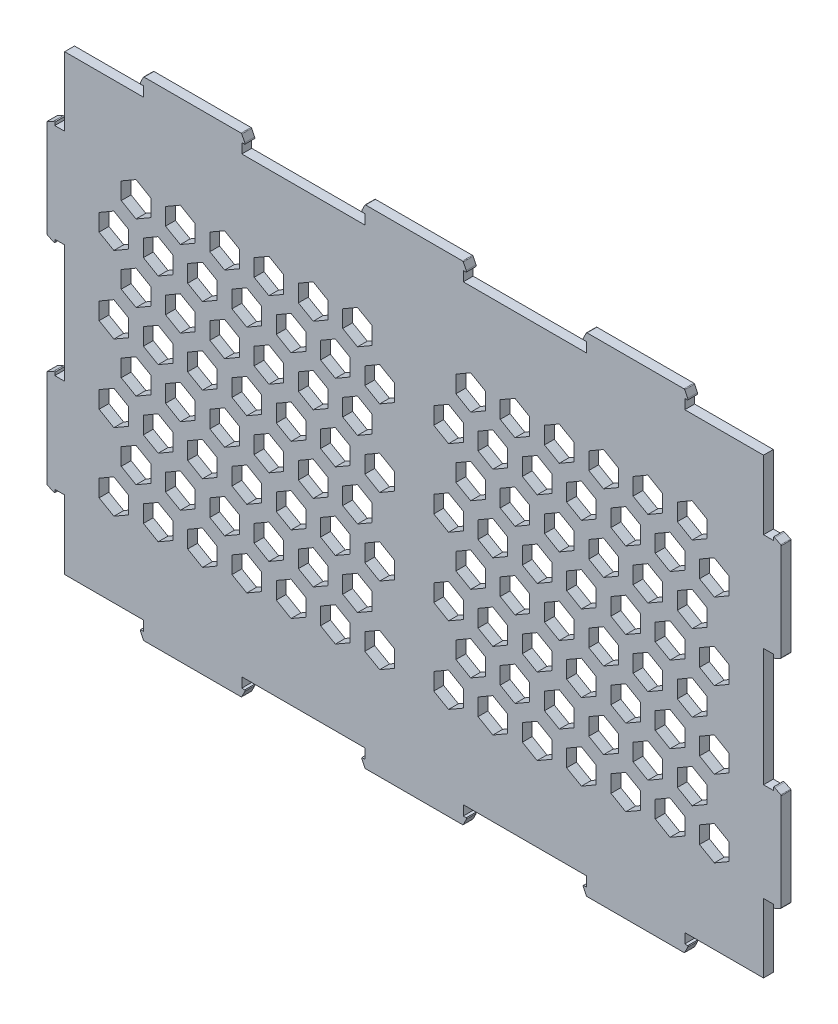
SolidWorks part; units mm, degrees
ref_plane "Front Plane" through (0, 0, 0) normal (0, 0, 1) x (1, 0, 0)
ref_plane "Top Plane" through (0, 0, 0) normal (0, 1, 0) x (1, 0, 0)
ref_plane "Right Plane" through (0, 0, 0) normal (1, 0, 0) x (0, 0, -1)
sketch "Sketch1" plane through (0, 0, 0) normal (0, 0, 1) x (1, 0, 0)
  line L0 (0, 0) -> (142, 0) construction
  line L1 (142, -46) -> (142, 46) construction
  line L2 (142, 46) -> (0, 46) construction
  line L3 (0, 46) -> (0, -46) construction
  line L8 (0, -46) -> (142, -46) construction
  line L30 (71, 46) -> (71, -46) construction
  line L31 (0, 32) -> (0, 46)
  line L32 (0, 46) -> (16, 46)
  line L35 (36, 46) -> (61, 46)
  line L37 (81, 46) -> (106, 46)
  line L39 (126, 46) -> (142, 46)
  line L40 (142, 46) -> (142, 32)
  line L42 (142, -32) -> (142, -46)
  line L43 (142, -46) -> (126, -46)
  line L46 (106, -46) -> (81, -46)
  line L48 (61, -46) -> (36, -46)
  line L50 (16, -46) -> (0, -46)
  line L51 (0, -46) -> (0, -32)
  line L52 (142, 46) -> (142, 32)
  line L54 (142, 12) -> (142, -12)
  line L56 (0, -12) -> (0, 12)
  line B0 (16, -46) -> (36, -46) construction
  line B1 (16.1618, -49.6) -> (35.8382, -49.6)
  line B2 (16, -46) -> (16, -48)
  line B3 (16, -49.5) -> (36, -49.5) construction
  line B4 (26, -49.5) -> (26, -46) construction
  line B5 (36, -46) -> (36, -48)
  line B6 (36.6, -48.3) -> (36, -49.5)
  line B7 (15.4, -48.3) -> (16, -49.5)
  line B8 (16, -48) -> (15.4, -48)
  line B9 (36, -48) -> (36.6, -48)
  arc B10 (16, -48) -> (15.4, -48.3) centre (15.7, -48.15) ccw construction
  arc B11 (16, -49.5) -> (16.1618, -49.6) centre (16.1618, -49.4191) ccw
  arc B12 (36, -49.5) -> (35.8382, -49.6) centre (35.8382, -49.4191) cw
  arc B13 (15.4, -48) -> (15.4, -48.3) centre (15.7, -48.15) ccw
  arc B14 (36.6, -48) -> (36.6, -48.3) centre (36.3, -48.15) cw
  line B15 (61, -46) -> (81, -46) construction
  line B16 (61.1618, -49.6) -> (80.8382, -49.6)
  line B17 (61, -46) -> (61, -48)
  line B18 (61, -49.5) -> (81, -49.5) construction
  line B19 (71, -49.5) -> (71, -46) construction
  line B20 (81, -46) -> (81, -48)
  line B21 (81.6, -48.3) -> (81, -49.5)
  line B22 (60.4, -48.3) -> (61, -49.5)
  line B23 (61, -48) -> (60.4, -48)
  line B24 (81, -48) -> (81.6, -48)
  arc B25 (61, -48) -> (60.4, -48.3) centre (60.7, -48.15) ccw construction
  arc B26 (61, -49.5) -> (61.1618, -49.6) centre (61.1618, -49.4191) ccw
  arc B27 (81, -49.5) -> (80.8382, -49.6) centre (80.8382, -49.4191) cw
  arc B28 (60.4, -48) -> (60.4, -48.3) centre (60.7, -48.15) ccw
  arc B29 (81.6, -48) -> (81.6, -48.3) centre (81.3, -48.15) cw
  line B30 (142, 12) -> (142, 32) construction
  line B31 (145.6, 12.1618) -> (145.6, 31.8382)
  line B32 (142, 12) -> (144, 12)
  line B33 (145.5, 12) -> (145.5, 32) construction
  line B34 (145.5, 22) -> (142, 22) construction
  line B35 (142, 32) -> (144, 32)
  line B36 (144.3, 32.6) -> (145.5, 32)
  line B37 (144.3, 11.4) -> (145.5, 12)
  line B38 (144, 12) -> (144, 11.4)
  line B39 (144, 32) -> (144, 32.6)
  arc B40 (144, 12) -> (144.3, 11.4) centre (144.15, 11.7) ccw construction
  arc B41 (145.5, 12) -> (145.6, 12.1618) centre (145.4191, 12.1618) ccw
  arc B42 (145.5, 32) -> (145.6, 31.8382) centre (145.4191, 31.8382) cw
  arc B43 (144, 11.4) -> (144.3, 11.4) centre (144.15, 11.7) ccw
  arc B44 (144, 32.6) -> (144.3, 32.6) centre (144.15, 32.3) cw
  line B45 (126, -46) -> (106, -46) construction
  line B46 (125.8382, -49.6) -> (106.1618, -49.6)
  line B47 (126, -46) -> (126, -48)
  line B48 (126, -49.5) -> (106, -49.5) construction
  line B49 (116, -49.5) -> (116, -46) construction
  line B50 (106, -46) -> (106, -48)
  line B51 (105.4, -48.3) -> (106, -49.5)
  line B52 (126.6, -48.3) -> (126, -49.5)
  line B53 (126, -48) -> (126.6, -48)
  line B54 (106, -48) -> (105.4, -48)
  arc B55 (126, -48) -> (126.6, -48.3) centre (126.3, -48.15) cw construction
  arc B56 (126, -49.5) -> (125.8382, -49.6) centre (125.8382, -49.4191) cw
  arc B57 (106, -49.5) -> (106.1618, -49.6) centre (106.1618, -49.4191) ccw
  arc B58 (126.6, -48) -> (126.6, -48.3) centre (126.3, -48.15) cw
  arc B59 (105.4, -48) -> (105.4, -48.3) centre (105.7, -48.15) ccw
  line B60 (16, 46) -> (36, 46) construction
  line B61 (16.1618, 49.6) -> (35.8382, 49.6)
  line B62 (16, 46) -> (16, 48)
  line B63 (16, 49.5) -> (36, 49.5) construction
  line B64 (26, 49.5) -> (26, 46) construction
  line B65 (36, 46) -> (36, 48)
  line B66 (36.6, 48.3) -> (36, 49.5)
  line B67 (15.4, 48.3) -> (16, 49.5)
  line B68 (16, 48) -> (15.4, 48)
  line B69 (36, 48) -> (36.6, 48)
  arc B70 (16, 48) -> (15.4, 48.3) centre (15.7, 48.15) cw construction
  arc B71 (16, 49.5) -> (16.1618, 49.6) centre (16.1618, 49.4191) cw
  arc B72 (36, 49.5) -> (35.8382, 49.6) centre (35.8382, 49.4191) ccw
  arc B73 (15.4, 48) -> (15.4, 48.3) centre (15.7, 48.15) cw
  arc B74 (36.6, 48) -> (36.6, 48.3) centre (36.3, 48.15) ccw
  line B75 (61, 46) -> (81, 46) construction
  line B76 (61.1618, 49.6) -> (80.8382, 49.6)
  line B77 (61, 46) -> (61, 48)
  line B78 (61, 49.5) -> (81, 49.5) construction
  line B79 (71, 49.5) -> (71, 46) construction
  line B80 (81, 46) -> (81, 48)
  line B81 (81.6, 48.3) -> (81, 49.5)
  line B82 (60.4, 48.3) -> (61, 49.5)
  line B83 (61, 48) -> (60.4, 48)
  line B84 (81, 48) -> (81.6, 48)
  arc B85 (61, 48) -> (60.4, 48.3) centre (60.7, 48.15) cw construction
  arc B86 (61, 49.5) -> (61.1618, 49.6) centre (61.1618, 49.4191) cw
  arc B87 (81, 49.5) -> (80.8382, 49.6) centre (80.8382, 49.4191) ccw
  arc B88 (60.4, 48) -> (60.4, 48.3) centre (60.7, 48.15) cw
  arc B89 (81.6, 48) -> (81.6, 48.3) centre (81.3, 48.15) ccw
  line B90 (126, 46) -> (106, 46) construction
  line B91 (125.8382, 49.6) -> (106.1618, 49.6)
  line B92 (126, 46) -> (126, 48)
  line B93 (126, 49.5) -> (106, 49.5) construction
  line B94 (116, 49.5) -> (116, 46) construction
  line B95 (106, 46) -> (106, 48)
  line B96 (105.4, 48.3) -> (106, 49.5)
  line B97 (126.6, 48.3) -> (126, 49.5)
  line B98 (126, 48) -> (126.6, 48)
  line B99 (106, 48) -> (105.4, 48)
  arc B100 (126, 48) -> (126.6, 48.3) centre (126.3, 48.15) ccw construction
  arc B101 (126, 49.5) -> (125.8382, 49.6) centre (125.8382, 49.4191) ccw
  arc B102 (106, 49.5) -> (106.1618, 49.6) centre (106.1618, 49.4191) cw
  arc B103 (126.6, 48) -> (126.6, 48.3) centre (126.3, 48.15) ccw
  arc B104 (105.4, 48) -> (105.4, 48.3) centre (105.7, 48.15) cw
  line B105 (0, 12) -> (0, 32) construction
  line B106 (-3.6, 12.1618) -> (-3.6, 31.8382)
  line B107 (0, 12) -> (-2, 12)
  line B108 (-3.5, 12) -> (-3.5, 32) construction
  line B109 (-3.5, 22) -> (0, 22) construction
  line B110 (0, 32) -> (-2, 32)
  line B111 (-2.3, 32.6) -> (-3.5, 32)
  line B112 (-2.3, 11.4) -> (-3.5, 12)
  line B113 (-2, 12) -> (-2, 11.4)
  line B114 (-2, 32) -> (-2, 32.6)
  arc B115 (-2, 12) -> (-2.3, 11.4) centre (-2.15, 11.7) cw construction
  arc B116 (-3.5, 12) -> (-3.6, 12.1618) centre (-3.4191, 12.1618) cw
  arc B117 (-3.5, 32) -> (-3.6, 31.8382) centre (-3.4191, 31.8382) ccw
  arc B118 (-2, 11.4) -> (-2.3, 11.4) centre (-2.15, 11.7) cw
  arc B119 (-2, 32.6) -> (-2.3, 32.6) centre (-2.15, 32.3) ccw
  line B120 (0, -12) -> (0, -32) construction
  line B121 (-3.6, -12.1618) -> (-3.6, -31.8382)
  line B122 (0, -12) -> (-2, -12)
  line B123 (-3.5, -12) -> (-3.5, -32) construction
  line B124 (-3.5, -22) -> (0, -22) construction
  line B125 (0, -32) -> (-2, -32)
  line B126 (-2.3, -32.6) -> (-3.5, -32)
  line B127 (-2.3, -11.4) -> (-3.5, -12)
  line B128 (-2, -12) -> (-2, -11.4)
  line B129 (-2, -32) -> (-2, -32.6)
  arc B130 (-2, -12) -> (-2.3, -11.4) centre (-2.15, -11.7) ccw construction
  arc B131 (-3.5, -12) -> (-3.6, -12.1618) centre (-3.4191, -12.1618) ccw
  arc B132 (-3.5, -32) -> (-3.6, -31.8382) centre (-3.4191, -31.8382) cw
  arc B133 (-2, -11.4) -> (-2.3, -11.4) centre (-2.15, -11.7) ccw
  arc B134 (-2, -32.6) -> (-2.3, -32.6) centre (-2.15, -32.3) cw
  line B135 (142, -12) -> (142, -32) construction
  line B136 (145.6, -12.1618) -> (145.6, -31.8382)
  line B137 (142, -12) -> (144, -12)
  line B138 (145.5, -12) -> (145.5, -32) construction
  line B139 (145.5, -22) -> (142, -22) construction
  line B140 (142, -32) -> (144, -32)
  line B141 (144.3, -32.6) -> (145.5, -32)
  line B142 (144.3, -11.4) -> (145.5, -12)
  line B143 (144, -12) -> (144, -11.4)
  line B144 (144, -32) -> (144, -32.6)
  arc B145 (144, -12) -> (144.3, -11.4) centre (144.15, -11.7) cw construction
  arc B146 (145.5, -12) -> (145.6, -12.1618) centre (145.4191, -12.1618) cw
  arc B147 (145.5, -32) -> (145.6, -31.8382) centre (145.4191, -31.8382) ccw
  arc B148 (144, -11.4) -> (144.3, -11.4) centre (144.15, -11.7) cw
  arc B149 (144, -32.6) -> (144.3, -32.6) centre (144.15, -32.3) ccw
  dimension "D2" = 22
  dimension "D3" = 45
  dimension "D1" = 142
  dimension "D4" = 92
sketch_block_instance "insert_bloquant_20mm-2mm-1"
sketch_block "insert_bloquant_20mm-2mm" parameters "D1"=2, "D2"=1.5, "D3"=1.2, "D4"=20, "D5"=0.1, "D6"=0.6
sketch_block_instance "insert_bloquant_20mm-2mm-2"
sketch_block_instance "insert_bloquant_20mm-2mm-4"
sketch_block_instance "insert_bloquant_20mm-2mm-6"
sketch_block_instance "insert_bloquant_20mm-2mm-7"
sketch_block_instance "insert_bloquant_20mm-2mm-8"
sketch_block_instance "insert_bloquant_20mm-2mm-9"
sketch_block_instance "insert_bloquant_20mm-2mm-13"
sketch_block_instance "insert_bloquant_20mm-2mm-14"
sketch_block_instance "insert_bloquant_20mm-2mm-15"
extrude "Boss-Extrude1" add sketch "Sketch1" along normal blind 2 contours B114 B119 B111 B117 B106 B116 B112 B118 B113 B107 L51 L50 B2 B8 B13 B7 B11 B1 B12 B6 B14 B9 B5 L48 B17 B23 B28 B22 B26 B16 B27 B21 B29 B24 B20 L46 B50 B54 B59 B51 B57 B46 B56 B52 B58 B53 B47 L43 L42 B32 B38 region at (71, 0, 0)
sketch "Esquisse1" plane through (0, 0, 2) normal (0, 0, 1) x (1, 0, 0)
  line L0 (142, 0) -> (0, 0) construction
  line L3 (84, 2.1651) -> (85.5, -2.1651) construction
  line L4 (142, 12) -> (142, -12) construction
  line L5 (71, 49.6) -> (71, -49.6) construction
  line L6 (61.1618, 49.6) -> (80.8382, 49.6) construction
  line L7 (61.1618, -49.6) -> (80.8382, -49.6) construction
  point P8 (84.75, 0)
  line B0 (135, 5.6292) -> (132, 7.3612)
  line B1 (132, 7.3612) -> (129, 5.6292)
  line B2 (124.5, 9.9593) -> (127.5, 8.2272)
  line B3 (130.5, 9.9593) -> (130.5, 13.4234)
  line B4 (130.5, 13.4234) -> (127.5, 15.1554)
  line B5 (127.5, 15.1554) -> (124.5, 13.4234)
  line B6 (126, 2.1651) -> (126, 5.6292)
  line B7 (126, 5.6292) -> (123, 7.3612)
  line B8 (123, 7.3612) -> (120, 5.6292)
  line B9 (115.5, 9.9593) -> (118.5, 8.2272)
  line B10 (121.5, 9.9593) -> (121.5, 13.4234)
  line B11 (121.5, 13.4234) -> (118.5, 15.1554)
  line B12 (118.5, 15.1554) -> (115.5, 13.4234)
  line B13 (111, 2.1651) -> (114, 0.433)
  line B14 (117, 2.1651) -> (117, 5.6292)
  line B15 (117, 5.6292) -> (114, 7.3612)
  line B16 (114, 7.3612) -> (111, 5.6292)
  line B17 (106.5, 9.9593) -> (109.5, 8.2272)
  line B18 (112.5, 9.9593) -> (112.5, 13.4234)
  line B19 (112.5, 13.4234) -> (109.5, 15.1554)
  line B20 (109.5, 15.1554) -> (106.5, 13.4234)
  line B21 (102, 2.1651) -> (105, 0.433)
  line B22 (99, 2.1651) -> (99, 5.6292)
  line B23 (132, 0.433) -> (135, 2.1651)
  line B24 (108, 2.1651) -> (108, 5.6292)
  line B25 (108, 5.6292) -> (105, 7.3612)
  line B26 (105, 7.3612) -> (102, 5.6292)
  line B27 (99, 5.6292) -> (96, 7.3612)
  line B28 (96, 7.3612) -> (93, 5.6292)
  line B29 (88.5, 9.9593) -> (91.5, 8.2272)
  line B30 (94.5, 9.9593) -> (94.5, 13.4234)
  line B31 (94.5, 13.4234) -> (91.5, 15.1554)
  line B32 (91.5, 15.1554) -> (88.5, 13.4234)
  line B33 (84, 2.1651) -> (87, 0.433)
  line B34 (90, 2.1651) -> (90, 5.6292)
  line B35 (90, 5.6292) -> (87, 7.3612)
  line B36 (87, 7.3612) -> (84, 5.6292)
  line B37 (79.5, 9.9593) -> (82.5, 8.2272)
  line B38 (85.5, 9.9593) -> (85.5, 13.4234)
  line B39 (85.5, 13.4234) -> (82.5, 15.1554)
  line B40 (82.5, 15.1554) -> (79.5, 13.4234)
  line B41 (75, 2.1651) -> (78, 0.433)
  line B42 (81, 2.1651) -> (81, 5.6292)
  line B43 (81, 5.6292) -> (78, 7.3612)
  line B44 (78, 7.3612) -> (75, 5.6292)
  line B45 (103.5, 13.4234) -> (100.5, 15.1554)
  line B46 (100.5, 15.1554) -> (97.5, 13.4234)
  line B47 (129, 2.1651) -> (132, 0.433)
  line B48 (135, 2.1651) -> (135, 5.6292)
  line B49 (129, 5.6292) -> (129, 2.1651)
  line B50 (127.5, 8.2272) -> (130.5, 9.9593)
  line B51 (124.5, 13.4234) -> (124.5, 9.9593)
  line B52 (84, 5.6292) -> (84, 2.1651)
  line B53 (87, 0.433) -> (90, 2.1651)
  line B54 (102, 5.6292) -> (102, 2.1651)
  line B55 (105, 0.433) -> (108, 2.1651)
  line B56 (120, 5.6292) -> (120, 2.1651)
  line B57 (120, 2.1651) -> (123, 0.433)
  line B58 (123, 0.433) -> (126, 2.1651)
  line B59 (115.5, 13.4234) -> (115.5, 9.9593)
  line B60 (118.5, 8.2272) -> (121.5, 9.9593)
  line B61 (78, 0.433) -> (81, 2.1651)
  line B62 (75, 5.6292) -> (75, 2.1651)
  line B63 (82.5, 8.2272) -> (85.5, 9.9593)
  line B64 (79.5, 13.4234) -> (79.5, 9.9593)
  line B65 (96, 0.433) -> (99, 2.1651)
  line B66 (93, 2.1651) -> (96, 0.433)
  line B67 (93, 5.6292) -> (93, 2.1651)
  line B68 (91.5, 8.2272) -> (94.5, 9.9593)
  line B69 (88.5, 13.4234) -> (88.5, 9.9593)
  line B70 (100.5, 8.2272) -> (103.5, 9.9593)
  line B71 (97.5, 9.9593) -> (100.5, 8.2272)
  line B72 (97.5, 13.4234) -> (97.5, 9.9593)
  line B73 (103.5, 9.9593) -> (103.5, 13.4234)
  line B74 (114, 0.433) -> (117, 2.1651)
  line B75 (111, 5.6292) -> (111, 2.1651)
  line B76 (109.5, 8.2272) -> (112.5, 9.9593)
  line B77 (106.5, 13.4234) -> (106.5, 9.9593)
  line B78 (135, 21.2176) -> (132, 22.9497)
  line B79 (132, 22.9497) -> (129, 21.2176)
  line B80 (124.5, 25.5477) -> (127.5, 23.8157)
  line B81 (130.5, 25.5477) -> (130.5, 29.0119)
  line B82 (130.5, 29.0119) -> (127.5, 30.7439)
  line B83 (127.5, 30.7439) -> (124.5, 29.0119)
  line B84 (126, 17.7535) -> (126, 21.2176)
  line B85 (126, 21.2176) -> (123, 22.9497)
  line B86 (123, 22.9497) -> (120, 21.2176)
  line B87 (115.5, 25.5477) -> (118.5, 23.8157)
  line B88 (121.5, 25.5477) -> (121.5, 29.0119)
  line B89 (121.5, 29.0119) -> (118.5, 30.7439)
  line B90 (118.5, 30.7439) -> (115.5, 29.0119)
  line B91 (111, 17.7535) -> (114, 16.0215)
  line B92 (117, 17.7535) -> (117, 21.2176)
  line B93 (117, 21.2176) -> (114, 22.9497)
  line B94 (114, 22.9497) -> (111, 21.2176)
  line B95 (106.5, 25.5477) -> (109.5, 23.8157)
  line B96 (112.5, 25.5477) -> (112.5, 29.0119)
  line B97 (112.5, 29.0119) -> (109.5, 30.7439)
  line B98 (109.5, 30.7439) -> (106.5, 29.0119)
  line B99 (102, 17.7535) -> (105, 16.0215)
  line B100 (99, 17.7535) -> (99, 21.2176)
  line B101 (132, 16.0215) -> (135, 17.7535)
  line B102 (108, 17.7535) -> (108, 21.2176)
  line B103 (108, 21.2176) -> (105, 22.9497)
  line B104 (105, 22.9497) -> (102, 21.2176)
  line B105 (99, 21.2176) -> (96, 22.9497)
  line B106 (96, 22.9497) -> (93, 21.2176)
  line B107 (88.5, 25.5477) -> (91.5, 23.8157)
  line B108 (94.5, 25.5477) -> (94.5, 29.0119)
  line B109 (94.5, 29.0119) -> (91.5, 30.7439)
  line B110 (91.5, 30.7439) -> (88.5, 29.0119)
  line B111 (84, 17.7535) -> (87, 16.0215)
  line B112 (90, 17.7535) -> (90, 21.2176)
  line B113 (90, 21.2176) -> (87, 22.9497)
  line B114 (87, 22.9497) -> (84, 21.2176)
  line B115 (79.5, 25.5477) -> (82.5, 23.8157)
  line B116 (85.5, 25.5477) -> (85.5, 29.0119)
  line B117 (85.5, 29.0119) -> (82.5, 30.7439)
  line B118 (82.5, 30.7439) -> (79.5, 29.0119)
  line B119 (75, 17.7535) -> (78, 16.0215)
  line B120 (81, 17.7535) -> (81, 21.2176)
  line B121 (81, 21.2176) -> (78, 22.9497)
  line B122 (78, 22.9497) -> (75, 21.2176)
  line B123 (103.5, 29.0119) -> (100.5, 30.7439)
  line B124 (100.5, 30.7439) -> (97.5, 29.0119)
  line B125 (129, 17.7535) -> (132, 16.0215)
  line B126 (135, 17.7535) -> (135, 21.2176)
  line B127 (129, 21.2176) -> (129, 17.7535)
  line B128 (127.5, 23.8157) -> (130.5, 25.5477)
  line B129 (124.5, 29.0119) -> (124.5, 25.5477)
  line B130 (84, 21.2176) -> (84, 17.7535)
  line B131 (87, 16.0215) -> (90, 17.7535)
  line B132 (102, 21.2176) -> (102, 17.7535)
  line B133 (105, 16.0215) -> (108, 17.7535)
  line B134 (120, 21.2176) -> (120, 17.7535)
  line B135 (120, 17.7535) -> (123, 16.0215)
  line B136 (123, 16.0215) -> (126, 17.7535)
  line B137 (115.5, 29.0119) -> (115.5, 25.5477)
  line B138 (118.5, 23.8157) -> (121.5, 25.5477)
  line B139 (78, 16.0215) -> (81, 17.7535)
  line B140 (75, 21.2176) -> (75, 17.7535)
  line B141 (82.5, 23.8157) -> (85.5, 25.5477)
  line B142 (79.5, 29.0119) -> (79.5, 25.5477)
  line B143 (96, 16.0215) -> (99, 17.7535)
  line B144 (93, 17.7535) -> (96, 16.0215)
  line B145 (93, 21.2176) -> (93, 17.7535)
  line B146 (91.5, 23.8157) -> (94.5, 25.5477)
  line B147 (88.5, 29.0119) -> (88.5, 25.5477)
  line B148 (100.5, 23.8157) -> (103.5, 25.5477)
  line B149 (97.5, 25.5477) -> (100.5, 23.8157)
  line B150 (97.5, 29.0119) -> (97.5, 25.5477)
  line B151 (103.5, 25.5477) -> (103.5, 29.0119)
  line B152 (114, 16.0215) -> (117, 17.7535)
  line B153 (111, 21.2176) -> (111, 17.7535)
  line B154 (109.5, 23.8157) -> (112.5, 25.5477)
  line B155 (106.5, 29.0119) -> (106.5, 25.5477)
  line B156 (135, -25.5477) -> (132, -23.8157)
  line B157 (132, -23.8157) -> (129, -25.5477)
  line B158 (124.5, -21.2176) -> (127.5, -22.9497)
  line B159 (130.5, -21.2176) -> (130.5, -17.7535)
  line B160 (130.5, -17.7535) -> (127.5, -16.0215)
  line B161 (127.5, -16.0215) -> (124.5, -17.7535)
  line B162 (126, -29.0119) -> (126, -25.5477)
  line B163 (126, -25.5477) -> (123, -23.8157)
  line B164 (123, -23.8157) -> (120, -25.5477)
  line B165 (115.5, -21.2176) -> (118.5, -22.9497)
  line B166 (121.5, -21.2176) -> (121.5, -17.7535)
  line B167 (121.5, -17.7535) -> (118.5, -16.0215)
  line B168 (118.5, -16.0215) -> (115.5, -17.7535)
  line B169 (111, -29.0119) -> (114, -30.7439)
  line B170 (117, -29.0119) -> (117, -25.5477)
  line B171 (117, -25.5477) -> (114, -23.8157)
  line B172 (114, -23.8157) -> (111, -25.5477)
  line B173 (106.5, -21.2176) -> (109.5, -22.9497)
  line B174 (112.5, -21.2176) -> (112.5, -17.7535)
  line B175 (112.5, -17.7535) -> (109.5, -16.0215)
  line B176 (109.5, -16.0215) -> (106.5, -17.7535)
  line B177 (102, -29.0119) -> (105, -30.7439)
  line B178 (99, -29.0119) -> (99, -25.5477)
  line B179 (132, -30.7439) -> (135, -29.0119)
  line B180 (108, -29.0119) -> (108, -25.5477)
  line B181 (108, -25.5477) -> (105, -23.8157)
  line B182 (105, -23.8157) -> (102, -25.5477)
  line B183 (99, -25.5477) -> (96, -23.8157)
  line B184 (96, -23.8157) -> (93, -25.5477)
  line B185 (88.5, -21.2176) -> (91.5, -22.9497)
  line B186 (94.5, -21.2176) -> (94.5, -17.7535)
  line B187 (94.5, -17.7535) -> (91.5, -16.0215)
  line B188 (91.5, -16.0215) -> (88.5, -17.7535)
  line B189 (84, -29.0119) -> (87, -30.7439)
  line B190 (90, -29.0119) -> (90, -25.5477)
  line B191 (90, -25.5477) -> (87, -23.8157)
  line B192 (87, -23.8157) -> (84, -25.5477)
  line B193 (79.5, -21.2176) -> (82.5, -22.9497)
  line B194 (85.5, -21.2176) -> (85.5, -17.7535)
  line B195 (85.5, -17.7535) -> (82.5, -16.0215)
  line B196 (82.5, -16.0215) -> (79.5, -17.7535)
  line B197 (75, -29.0119) -> (78, -30.7439)
  line B198 (81, -29.0119) -> (81, -25.5477)
  line B199 (81, -25.5477) -> (78, -23.8157)
  line B200 (78, -23.8157) -> (75, -25.5477)
  line B201 (103.5, -17.7535) -> (100.5, -16.0215)
  line B202 (100.5, -16.0215) -> (97.5, -17.7535)
  line B203 (129, -29.0119) -> (132, -30.7439)
  line B204 (135, -29.0119) -> (135, -25.5477)
  line B205 (129, -25.5477) -> (129, -29.0119)
  line B206 (127.5, -22.9497) -> (130.5, -21.2176)
  line B207 (124.5, -17.7535) -> (124.5, -21.2176)
  line B208 (84, -25.5477) -> (84, -29.0119)
  line B209 (87, -30.7439) -> (90, -29.0119)
  line B210 (102, -25.5477) -> (102, -29.0119)
  line B211 (105, -30.7439) -> (108, -29.0119)
  line B212 (132, -27.2798) -> (75, -27.2798) construction
  line B213 (120, -25.5477) -> (120, -29.0119)
  line B214 (120, -29.0119) -> (123, -30.7439)
  line B215 (123, -30.7439) -> (126, -29.0119)
  line B216 (115.5, -17.7535) -> (115.5, -21.2176)
  line B217 (118.5, -22.9497) -> (121.5, -21.2176)
  line B218 (78, -30.7439) -> (81, -29.0119)
  line B219 (75, -25.5477) -> (75, -29.0119)
  line B220 (82.5, -22.9497) -> (85.5, -21.2176)
  line B221 (79.5, -17.7535) -> (79.5, -21.2176)
  line B222 (96, -30.7439) -> (99, -29.0119)
  line B223 (93, -29.0119) -> (96, -30.7439)
  line B224 (93, -25.5477) -> (93, -29.0119)
  line B225 (91.5, -22.9497) -> (94.5, -21.2176)
  line B226 (88.5, -17.7535) -> (88.5, -21.2176)
  line B227 (100.5, -22.9497) -> (103.5, -21.2176)
  line B228 (97.5, -21.2176) -> (100.5, -22.9497)
  line B229 (97.5, -17.7535) -> (97.5, -21.2176)
  line B230 (103.5, -21.2176) -> (103.5, -17.7535)
  line B231 (114, -30.7439) -> (117, -29.0119)
  line B232 (111, -25.5477) -> (111, -29.0119)
  line B233 (109.5, -22.9497) -> (112.5, -21.2176)
  line B234 (106.5, -17.7535) -> (106.5, -21.2176)
  line B235 (135, -9.9593) -> (132, -8.2272)
  line B236 (132, -8.2272) -> (129, -9.9593)
  line B237 (124.5, -5.6292) -> (127.5, -7.3612)
  line B238 (130.5, -5.6292) -> (130.5, -2.1651)
  line B239 (130.5, -2.1651) -> (127.5, -0.433)
  line B240 (127.5, -0.433) -> (124.5, -2.1651)
  line B241 (126, -13.4234) -> (126, -9.9593)
  line B242 (126, -9.9593) -> (123, -8.2272)
  line B243 (123, -8.2272) -> (120, -9.9593)
  line B244 (115.5, -5.6292) -> (118.5, -7.3612)
  line B245 (121.5, -5.6292) -> (121.5, -2.1651)
  line B246 (121.5, -2.1651) -> (118.5, -0.433)
  line B247 (118.5, -0.433) -> (115.5, -2.1651)
  line B248 (111, -13.4234) -> (114, -15.1554)
  line B249 (117, -13.4234) -> (117, -9.9593)
  line B250 (117, -9.9593) -> (114, -8.2272)
  line B251 (114, -8.2272) -> (111, -9.9593)
  line B252 (106.5, -5.6292) -> (109.5, -7.3612)
  line B253 (112.5, -5.6292) -> (112.5, -2.1651)
  line B254 (112.5, -2.1651) -> (109.5, -0.433)
  line B255 (109.5, -0.433) -> (106.5, -2.1651)
  line B256 (102, -13.4234) -> (105, -15.1554)
  line B257 (99, -13.4234) -> (99, -9.9593)
  line B258 (132, -15.1554) -> (135, -13.4234)
  line B259 (108, -13.4234) -> (108, -9.9593)
  line B260 (108, -9.9593) -> (105, -8.2272)
  line B261 (105, -8.2272) -> (102, -9.9593)
  line B262 (99, -9.9593) -> (96, -8.2272)
  line B263 (96, -8.2272) -> (93, -9.9593)
  line B264 (88.5, -5.6292) -> (91.5, -7.3612)
  line B265 (94.5, -5.6292) -> (94.5, -2.1651)
  line B266 (94.5, -2.1651) -> (91.5, -0.433)
  line B267 (91.5, -0.433) -> (88.5, -2.1651)
  line B268 (84, -13.4234) -> (87, -15.1554)
  line B269 (90, -13.4234) -> (90, -9.9593)
  line B270 (90, -9.9593) -> (87, -8.2272)
  line B271 (87, -8.2272) -> (84, -9.9593)
  line B272 (79.5, -5.6292) -> (82.5, -7.3612)
  line B273 (85.5, -5.6292) -> (85.5, -2.1651)
  line B274 (85.5, -2.1651) -> (82.5, -0.433)
  line B275 (82.5, -0.433) -> (79.5, -2.1651)
  line B276 (75, -13.4234) -> (78, -15.1554)
  line B277 (81, -13.4234) -> (81, -9.9593)
  line B278 (81, -9.9593) -> (78, -8.2272)
  line B279 (78, -8.2272) -> (75, -9.9593)
  line B280 (103.5, -2.1651) -> (100.5, -0.433)
  line B281 (100.5, -0.433) -> (97.5, -2.1651)
  line B282 (129, -13.4234) -> (132, -15.1554)
  line B283 (135, -13.4234) -> (135, -9.9593)
  line B284 (129, -9.9593) -> (129, -13.4234)
  line B285 (127.5, -7.3612) -> (130.5, -5.6292)
  line B286 (124.5, -2.1651) -> (124.5, -5.6292)
  line B287 (84, -9.9593) -> (84, -13.4234)
  line B288 (87, -15.1554) -> (90, -13.4234)
  line B289 (102, -9.9593) -> (102, -13.4234)
  line B290 (105, -15.1554) -> (108, -13.4234)
  line B291 (132, -11.6913) -> (75, -11.6913) construction
  line B292 (120, -9.9593) -> (120, -13.4234)
  line B293 (120, -13.4234) -> (123, -15.1554)
  line B294 (123, -15.1554) -> (126, -13.4234)
  line B295 (115.5, -2.1651) -> (115.5, -5.6292)
  line B296 (118.5, -7.3612) -> (121.5, -5.6292)
  line B297 (78, -15.1554) -> (81, -13.4234)
  line B298 (75, -9.9593) -> (75, -13.4234)
  line B299 (82.5, -7.3612) -> (85.5, -5.6292)
  line B300 (79.5, -2.1651) -> (79.5, -5.6292)
  line B301 (96, -15.1554) -> (99, -13.4234)
  line B302 (93, -13.4234) -> (96, -15.1554)
  line B303 (93, -9.9593) -> (93, -13.4234)
  line B304 (91.5, -7.3612) -> (94.5, -5.6292)
  line B305 (88.5, -2.1651) -> (88.5, -5.6292)
  line B306 (100.5, -7.3612) -> (103.5, -5.6292)
  line B307 (97.5, -5.6292) -> (100.5, -7.3612)
  line B308 (97.5, -2.1651) -> (97.5, -5.6292)
  line B309 (103.5, -5.6292) -> (103.5, -2.1651)
  line B310 (114, -15.1554) -> (117, -13.4234)
  line B311 (111, -9.9593) -> (111, -13.4234)
  line B312 (109.5, -7.3612) -> (112.5, -5.6292)
  line B313 (106.5, -2.1651) -> (106.5, -5.6292)
  line B314 (7, 5.6292) -> (10, 7.3612)
  line B315 (10, 7.3612) -> (13, 5.6292)
  line B316 (17.5, 9.9593) -> (14.5, 8.2272)
  line B317 (11.5, 9.9593) -> (11.5, 13.4234)
  line B318 (11.5, 13.4234) -> (14.5, 15.1554)
  line B319 (14.5, 15.1554) -> (17.5, 13.4234)
  line B320 (16, 2.1651) -> (16, 5.6292)
  line B321 (16, 5.6292) -> (19, 7.3612)
  line B322 (19, 7.3612) -> (22, 5.6292)
  line B323 (26.5, 9.9593) -> (23.5, 8.2272)
  line B324 (20.5, 9.9593) -> (20.5, 13.4234)
  line B325 (20.5, 13.4234) -> (23.5, 15.1554)
  line B326 (23.5, 15.1554) -> (26.5, 13.4234)
  line B327 (31, 2.1651) -> (28, 0.433)
  line B328 (25, 2.1651) -> (25, 5.6292)
  line B329 (25, 5.6292) -> (28, 7.3612)
  line B330 (28, 7.3612) -> (31, 5.6292)
  line B331 (35.5, 9.9593) -> (32.5, 8.2272)
  line B332 (29.5, 9.9593) -> (29.5, 13.4234)
  line B333 (29.5, 13.4234) -> (32.5, 15.1554)
  line B334 (32.5, 15.1554) -> (35.5, 13.4234)
  line B335 (40, 2.1651) -> (37, 0.433)
  line B336 (43, 2.1651) -> (43, 5.6292)
  line B337 (10, 0.433) -> (7, 2.1651)
  line B338 (34, 2.1651) -> (34, 5.6292)
  line B339 (34, 5.6292) -> (37, 7.3612)
  line B340 (37, 7.3612) -> (40, 5.6292)
  line B341 (43, 5.6292) -> (46, 7.3612)
  line B342 (46, 7.3612) -> (49, 5.6292)
  line B343 (53.5, 9.9593) -> (50.5, 8.2272)
  line B344 (47.5, 9.9593) -> (47.5, 13.4234)
  line B345 (47.5, 13.4234) -> (50.5, 15.1554)
  line B346 (50.5, 15.1554) -> (53.5, 13.4234)
  line B347 (58, 2.1651) -> (55, 0.433)
  line B348 (52, 2.1651) -> (52, 5.6292)
  line B349 (52, 5.6292) -> (55, 7.3612)
  line B350 (55, 7.3612) -> (58, 5.6292)
  line B351 (62.5, 9.9593) -> (59.5, 8.2272)
  line B352 (56.5, 9.9593) -> (56.5, 13.4234)
  line B353 (56.5, 13.4234) -> (59.5, 15.1554)
  line B354 (59.5, 15.1554) -> (62.5, 13.4234)
  line B355 (67, 2.1651) -> (64, 0.433)
  line B356 (61, 2.1651) -> (61, 5.6292)
  line B357 (61, 5.6292) -> (64, 7.3612)
  line B358 (64, 7.3612) -> (67, 5.6292)
  line B359 (38.5, 13.4234) -> (41.5, 15.1554)
  line B360 (41.5, 15.1554) -> (44.5, 13.4234)
  line B361 (13, 2.1651) -> (10, 0.433)
  line B362 (7, 2.1651) -> (7, 5.6292)
  line B363 (13, 5.6292) -> (13, 2.1651)
  line B364 (14.5, 8.2272) -> (11.5, 9.9593)
  line B365 (17.5, 13.4234) -> (17.5, 9.9593)
  line B366 (58, 5.6292) -> (58, 2.1651)
  line B367 (55, 0.433) -> (52, 2.1651)
  line B368 (40, 5.6292) -> (40, 2.1651)
  line B369 (37, 0.433) -> (34, 2.1651)
  line B370 (22, 5.6292) -> (22, 2.1651)
  line B371 (22, 2.1651) -> (19, 0.433)
  line B372 (19, 0.433) -> (16, 2.1651)
  line B373 (26.5, 13.4234) -> (26.5, 9.9593)
  line B374 (23.5, 8.2272) -> (20.5, 9.9593)
  line B375 (64, 0.433) -> (61, 2.1651)
  line B376 (67, 5.6292) -> (67, 2.1651)
  line B377 (59.5, 8.2272) -> (56.5, 9.9593)
  line B378 (62.5, 13.4234) -> (62.5, 9.9593)
  line B379 (46, 0.433) -> (43, 2.1651)
  line B380 (49, 2.1651) -> (46, 0.433)
  line B381 (49, 5.6292) -> (49, 2.1651)
  line B382 (50.5, 8.2272) -> (47.5, 9.9593)
  line B383 (53.5, 13.4234) -> (53.5, 9.9593)
  line B384 (41.5, 8.2272) -> (38.5, 9.9593)
  line B385 (44.5, 9.9593) -> (41.5, 8.2272)
  line B386 (44.5, 13.4234) -> (44.5, 9.9593)
  line B387 (38.5, 9.9593) -> (38.5, 13.4234)
  line B388 (28, 0.433) -> (25, 2.1651)
  line B389 (31, 5.6292) -> (31, 2.1651)
  line B390 (32.5, 8.2272) -> (29.5, 9.9593)
  line B391 (35.5, 13.4234) -> (35.5, 9.9593)
  line B392 (7, 21.2176) -> (10, 22.9497)
  line B393 (10, 22.9497) -> (13, 21.2176)
  line B394 (17.5, 25.5477) -> (14.5, 23.8157)
  line B395 (11.5, 25.5477) -> (11.5, 29.0119)
  line B396 (11.5, 29.0119) -> (14.5, 30.7439)
  line B397 (14.5, 30.7439) -> (17.5, 29.0119)
  line B398 (16, 17.7535) -> (16, 21.2176)
  line B399 (16, 21.2176) -> (19, 22.9497)
  line B400 (19, 22.9497) -> (22, 21.2176)
  line B401 (26.5, 25.5477) -> (23.5, 23.8157)
  line B402 (20.5, 25.5477) -> (20.5, 29.0119)
  line B403 (20.5, 29.0119) -> (23.5, 30.7439)
  line B404 (23.5, 30.7439) -> (26.5, 29.0119)
  line B405 (31, 17.7535) -> (28, 16.0215)
  line B406 (25, 17.7535) -> (25, 21.2176)
  line B407 (25, 21.2176) -> (28, 22.9497)
  line B408 (28, 22.9497) -> (31, 21.2176)
  line B409 (35.5, 25.5477) -> (32.5, 23.8157)
  line B410 (29.5, 25.5477) -> (29.5, 29.0119)
  line B411 (29.5, 29.0119) -> (32.5, 30.7439)
  line B412 (32.5, 30.7439) -> (35.5, 29.0119)
  line B413 (40, 17.7535) -> (37, 16.0215)
  line B414 (43, 17.7535) -> (43, 21.2176)
  line B415 (10, 16.0215) -> (7, 17.7535)
  line B416 (34, 17.7535) -> (34, 21.2176)
  line B417 (34, 21.2176) -> (37, 22.9497)
  line B418 (37, 22.9497) -> (40, 21.2176)
  line B419 (43, 21.2176) -> (46, 22.9497)
  line B420 (46, 22.9497) -> (49, 21.2176)
  line B421 (53.5, 25.5477) -> (50.5, 23.8157)
  line B422 (47.5, 25.5477) -> (47.5, 29.0119)
  line B423 (47.5, 29.0119) -> (50.5, 30.7439)
  line B424 (50.5, 30.7439) -> (53.5, 29.0119)
  line B425 (58, 17.7535) -> (55, 16.0215)
  line B426 (52, 17.7535) -> (52, 21.2176)
  line B427 (52, 21.2176) -> (55, 22.9497)
  line B428 (55, 22.9497) -> (58, 21.2176)
  line B429 (62.5, 25.5477) -> (59.5, 23.8157)
  line B430 (56.5, 25.5477) -> (56.5, 29.0119)
  line B431 (56.5, 29.0119) -> (59.5, 30.7439)
  line B432 (59.5, 30.7439) -> (62.5, 29.0119)
  line B433 (67, 17.7535) -> (64, 16.0215)
  line B434 (61, 17.7535) -> (61, 21.2176)
  line B435 (61, 21.2176) -> (64, 22.9497)
  line B436 (64, 22.9497) -> (67, 21.2176)
  line B437 (38.5, 29.0119) -> (41.5, 30.7439)
  line B438 (41.5, 30.7439) -> (44.5, 29.0119)
  line B439 (13, 17.7535) -> (10, 16.0215)
  line B440 (7, 17.7535) -> (7, 21.2176)
  line B441 (13, 21.2176) -> (13, 17.7535)
  line B442 (14.5, 23.8157) -> (11.5, 25.5477)
  line B443 (17.5, 29.0119) -> (17.5, 25.5477)
  line B444 (58, 21.2176) -> (58, 17.7535)
  line B445 (55, 16.0215) -> (52, 17.7535)
  line B446 (40, 21.2176) -> (40, 17.7535)
  line B447 (37, 16.0215) -> (34, 17.7535)
  line B448 (22, 21.2176) -> (22, 17.7535)
  line B449 (22, 17.7535) -> (19, 16.0215)
  line B450 (19, 16.0215) -> (16, 17.7535)
  line B451 (26.5, 29.0119) -> (26.5, 25.5477)
  line B452 (23.5, 23.8157) -> (20.5, 25.5477)
  line B453 (64, 16.0215) -> (61, 17.7535)
  line B454 (67, 21.2176) -> (67, 17.7535)
  line B455 (59.5, 23.8157) -> (56.5, 25.5477)
  line B456 (62.5, 29.0119) -> (62.5, 25.5477)
  line B457 (46, 16.0215) -> (43, 17.7535)
  line B458 (49, 17.7535) -> (46, 16.0215)
  line B459 (49, 21.2176) -> (49, 17.7535)
  line B460 (50.5, 23.8157) -> (47.5, 25.5477)
  line B461 (53.5, 29.0119) -> (53.5, 25.5477)
  line B462 (41.5, 23.8157) -> (38.5, 25.5477)
  line B463 (44.5, 25.5477) -> (41.5, 23.8157)
  line B464 (44.5, 29.0119) -> (44.5, 25.5477)
  line B465 (38.5, 25.5477) -> (38.5, 29.0119)
  line B466 (28, 16.0215) -> (25, 17.7535)
  line B467 (31, 21.2176) -> (31, 17.7535)
  line B468 (32.5, 23.8157) -> (29.5, 25.5477)
  line B469 (35.5, 29.0119) -> (35.5, 25.5477)
  line B470 (7, -9.9593) -> (10, -8.2272)
  line B471 (10, -8.2272) -> (13, -9.9593)
  line B472 (17.5, -5.6292) -> (14.5, -7.3612)
  line B473 (11.5, -5.6292) -> (11.5, -2.1651)
  line B474 (11.5, -2.1651) -> (14.5, -0.433)
  line B475 (14.5, -0.433) -> (17.5, -2.1651)
  line B476 (16, -13.4234) -> (16, -9.9593)
  line B477 (16, -9.9593) -> (19, -8.2272)
  line B478 (19, -8.2272) -> (22, -9.9593)
  line B479 (26.5, -5.6292) -> (23.5, -7.3612)
  line B480 (20.5, -5.6292) -> (20.5, -2.1651)
  line B481 (20.5, -2.1651) -> (23.5, -0.433)
  line B482 (23.5, -0.433) -> (26.5, -2.1651)
  line B483 (31, -13.4234) -> (28, -15.1554)
  line B484 (25, -13.4234) -> (25, -9.9593)
  line B485 (25, -9.9593) -> (28, -8.2272)
  line B486 (28, -8.2272) -> (31, -9.9593)
  line B487 (35.5, -5.6292) -> (32.5, -7.3612)
  line B488 (29.5, -5.6292) -> (29.5, -2.1651)
  line B489 (29.5, -2.1651) -> (32.5, -0.433)
  line B490 (32.5, -0.433) -> (35.5, -2.1651)
  line B491 (40, -13.4234) -> (37, -15.1554)
  line B492 (43, -13.4234) -> (43, -9.9593)
  line B493 (10, -15.1554) -> (7, -13.4234)
  line B494 (34, -13.4234) -> (34, -9.9593)
  line B495 (34, -9.9593) -> (37, -8.2272)
  line B496 (37, -8.2272) -> (40, -9.9593)
  line B497 (43, -9.9593) -> (46, -8.2272)
  line B498 (46, -8.2272) -> (49, -9.9593)
  line B499 (53.5, -5.6292) -> (50.5, -7.3612)
  line B500 (47.5, -5.6292) -> (47.5, -2.1651)
  line B501 (47.5, -2.1651) -> (50.5, -0.433)
  line B502 (50.5, -0.433) -> (53.5, -2.1651)
  line B503 (58, -13.4234) -> (55, -15.1554)
  line B504 (52, -13.4234) -> (52, -9.9593)
  line B505 (52, -9.9593) -> (55, -8.2272)
  line B506 (55, -8.2272) -> (58, -9.9593)
  line B507 (62.5, -5.6292) -> (59.5, -7.3612)
  line B508 (56.5, -5.6292) -> (56.5, -2.1651)
  line B509 (56.5, -2.1651) -> (59.5, -0.433)
  line B510 (59.5, -0.433) -> (62.5, -2.1651)
  line B511 (67, -13.4234) -> (64, -15.1554)
  line B512 (61, -13.4234) -> (61, -9.9593)
  line B513 (61, -9.9593) -> (64, -8.2272)
  line B514 (64, -8.2272) -> (67, -9.9593)
  line B515 (38.5, -2.1651) -> (41.5, -0.433)
  line B516 (41.5, -0.433) -> (44.5, -2.1651)
  line B517 (13, -13.4234) -> (10, -15.1554)
  line B518 (7, -13.4234) -> (7, -9.9593)
  line B519 (13, -9.9593) -> (13, -13.4234)
  line B520 (14.5, -7.3612) -> (11.5, -5.6292)
  line B521 (17.5, -2.1651) -> (17.5, -5.6292)
  line B522 (58, -9.9593) -> (58, -13.4234)
  line B523 (55, -15.1554) -> (52, -13.4234)
  line B524 (40, -9.9593) -> (40, -13.4234)
  line B525 (37, -15.1554) -> (34, -13.4234)
  line B526 (22, -9.9593) -> (22, -13.4234)
  line B527 (22, -13.4234) -> (19, -15.1554)
  line B528 (19, -15.1554) -> (16, -13.4234)
  line B529 (26.5, -2.1651) -> (26.5, -5.6292)
  line B530 (23.5, -7.3612) -> (20.5, -5.6292)
  line B531 (64, -15.1554) -> (61, -13.4234)
  line B532 (67, -9.9593) -> (67, -13.4234)
  line B533 (59.5, -7.3612) -> (56.5, -5.6292)
  line B534 (62.5, -2.1651) -> (62.5, -5.6292)
  line B535 (46, -15.1554) -> (43, -13.4234)
  line B536 (49, -13.4234) -> (46, -15.1554)
  line B537 (49, -9.9593) -> (49, -13.4234)
  line B538 (50.5, -7.3612) -> (47.5, -5.6292)
  line B539 (53.5, -2.1651) -> (53.5, -5.6292)
  line B540 (41.5, -7.3612) -> (38.5, -5.6292)
  line B541 (44.5, -5.6292) -> (41.5, -7.3612)
  line B542 (44.5, -2.1651) -> (44.5, -5.6292)
  line B543 (38.5, -5.6292) -> (38.5, -2.1651)
  line B544 (28, -15.1554) -> (25, -13.4234)
  line B545 (31, -9.9593) -> (31, -13.4234)
  line B546 (32.5, -7.3612) -> (29.5, -5.6292)
  line B547 (35.5, -2.1651) -> (35.5, -5.6292)
  line B548 (7, -25.5477) -> (10, -23.8157)
  line B549 (10, -23.8157) -> (13, -25.5477)
  line B550 (17.5, -21.2176) -> (14.5, -22.9497)
  line B551 (11.5, -21.2176) -> (11.5, -17.7535)
  line B552 (11.5, -17.7535) -> (14.5, -16.0215)
  line B553 (14.5, -16.0215) -> (17.5, -17.7535)
  line B554 (16, -29.0119) -> (16, -25.5477)
  line B555 (16, -25.5477) -> (19, -23.8157)
  line B556 (19, -23.8157) -> (22, -25.5477)
  line B557 (26.5, -21.2176) -> (23.5, -22.9497)
  line B558 (20.5, -21.2176) -> (20.5, -17.7535)
  line B559 (20.5, -17.7535) -> (23.5, -16.0215)
  line B560 (23.5, -16.0215) -> (26.5, -17.7535)
  line B561 (31, -29.0119) -> (28, -30.7439)
  line B562 (25, -29.0119) -> (25, -25.5477)
  line B563 (25, -25.5477) -> (28, -23.8157)
  line B564 (28, -23.8157) -> (31, -25.5477)
  line B565 (35.5, -21.2176) -> (32.5, -22.9497)
  line B566 (29.5, -21.2176) -> (29.5, -17.7535)
  line B567 (29.5, -17.7535) -> (32.5, -16.0215)
  line B568 (32.5, -16.0215) -> (35.5, -17.7535)
  line B569 (40, -29.0119) -> (37, -30.7439)
  line B570 (43, -29.0119) -> (43, -25.5477)
  line B571 (10, -30.7439) -> (7, -29.0119)
  line B572 (34, -29.0119) -> (34, -25.5477)
  line B573 (34, -25.5477) -> (37, -23.8157)
  line B574 (37, -23.8157) -> (40, -25.5477)
  line B575 (43, -25.5477) -> (46, -23.8157)
  line B576 (46, -23.8157) -> (49, -25.5477)
  line B577 (53.5, -21.2176) -> (50.5, -22.9497)
  line B578 (47.5, -21.2176) -> (47.5, -17.7535)
  line B579 (47.5, -17.7535) -> (50.5, -16.0215)
  line B580 (50.5, -16.0215) -> (53.5, -17.7535)
  line B581 (58, -29.0119) -> (55, -30.7439)
  line B582 (52, -29.0119) -> (52, -25.5477)
  line B583 (52, -25.5477) -> (55, -23.8157)
  line B584 (55, -23.8157) -> (58, -25.5477)
  line B585 (62.5, -21.2176) -> (59.5, -22.9497)
  line B586 (56.5, -21.2176) -> (56.5, -17.7535)
  line B587 (56.5, -17.7535) -> (59.5, -16.0215)
  line B588 (59.5, -16.0215) -> (62.5, -17.7535)
  line B589 (67, -29.0119) -> (64, -30.7439)
  line B590 (61, -29.0119) -> (61, -25.5477)
  line B591 (61, -25.5477) -> (64, -23.8157)
  line B592 (64, -23.8157) -> (67, -25.5477)
  line B593 (38.5, -17.7535) -> (41.5, -16.0215)
  line B594 (41.5, -16.0215) -> (44.5, -17.7535)
  line B595 (13, -29.0119) -> (10, -30.7439)
  line B596 (7, -29.0119) -> (7, -25.5477)
  line B597 (13, -25.5477) -> (13, -29.0119)
  line B598 (14.5, -22.9497) -> (11.5, -21.2176)
  line B599 (17.5, -17.7535) -> (17.5, -21.2176)
  line B600 (58, -25.5477) -> (58, -29.0119)
  line B601 (55, -30.7439) -> (52, -29.0119)
  line B602 (40, -25.5477) -> (40, -29.0119)
  line B603 (37, -30.7439) -> (34, -29.0119)
  line B604 (22, -25.5477) -> (22, -29.0119)
  line B605 (22, -29.0119) -> (19, -30.7439)
  line B606 (19, -30.7439) -> (16, -29.0119)
  line B607 (26.5, -17.7535) -> (26.5, -21.2176)
  line B608 (23.5, -22.9497) -> (20.5, -21.2176)
  line B609 (64, -30.7439) -> (61, -29.0119)
  line B610 (67, -25.5477) -> (67, -29.0119)
  line B611 (59.5, -22.9497) -> (56.5, -21.2176)
  line B612 (62.5, -17.7535) -> (62.5, -21.2176)
  line B613 (46, -30.7439) -> (43, -29.0119)
  line B614 (49, -29.0119) -> (46, -30.7439)
  line B615 (49, -25.5477) -> (49, -29.0119)
  line B616 (50.5, -22.9497) -> (47.5, -21.2176)
  line B617 (53.5, -17.7535) -> (53.5, -21.2176)
  line B618 (41.5, -22.9497) -> (38.5, -21.2176)
  line B619 (44.5, -21.2176) -> (41.5, -22.9497)
  line B620 (44.5, -17.7535) -> (44.5, -21.2176)
  line B621 (38.5, -21.2176) -> (38.5, -17.7535)
  line B622 (28, -30.7439) -> (25, -29.0119)
  line B623 (31, -25.5477) -> (31, -29.0119)
  line B624 (32.5, -22.9497) -> (29.5, -21.2176)
  line B625 (35.5, -17.7535) -> (35.5, -21.2176)
  dimension "D1" = 4
sketch_block_instance "Alveole_9mm_3mm_8x2-4"
sketch_block "Alveole_9mm_3mm_8x2" parameters "D1"=7, "D2"=1.5, "D3"=13.2857, "D4"=14
sketch_block_instance "Alveole_9mm_3mm_8x2-5"
sketch_block_instance "Alveole_9mm_3mm_8x2-10"
sketch_block_instance "Alveole_9mm_3mm_8x2-11"
sketch_block_instance "Alveole_9mm_3mm_8x2-12"
sketch_block_instance "Alveole_9mm_3mm_8x2-13"
sketch_block_instance "Alveole_9mm_3mm_8x2-14"
sketch_block_instance "Alveole_9mm_3mm_8x2-15"
extrude "Enlèv. mat.-Extru.1" cut sketch "Esquisse1" against normal through all
